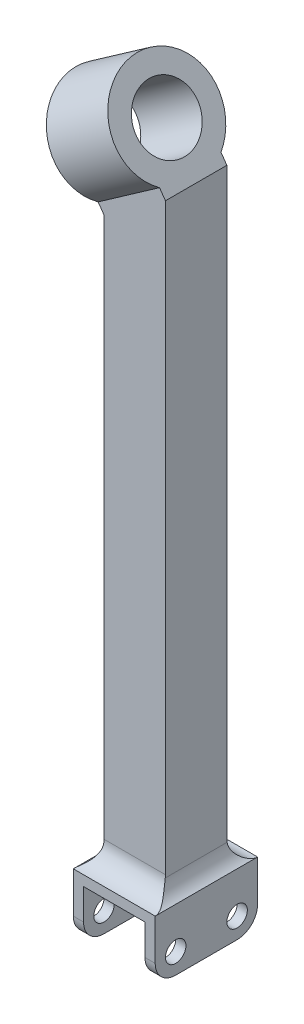
SolidWorks part; units mm, degrees
ref_plane "Front Plane" through (0, 0, 0) normal (0, 0, 1) x (1, 0, 0)
ref_plane "Top Plane" through (0, 0, 0) normal (0, 1, 0) x (1, 0, 0)
ref_plane "Right Plane" through (0, 0, 0) normal (1, 0, 0) x (0, 0, -1)
sketch "Sketch1" plane through (0, 0, 0) normal (0, 0, 1) x (1, 0, 0)
  line L0 (0, 0) -> (30, 0)
  line L1 (30, 0) -> (30, 300)
  line L2 (30, 300) -> (1.3212, 340.9576)
  line L3 (1.3212, 340.9576) -> (-28.6788, 319.9514)
  line L4 (30, 300) -> (0, 278.9938) construction
  line L5 (0, 0) -> (0, 278.9938)
  line L6 (0, 278.9938) -> (-28.6788, 319.9514)
  dimension "D1" = 30
  dimension "D2" = 300
  dimension "D3" = 215
  dimension "D4" = 50
  dimension "D5" = 55
extrude "Boss-Extrude1" add sketch "Sketch1" along normal blind 50
sketch "Sketch2" plane through (161.0842, 112.7924, 0) normal (0.8192, 0.5736, 0) x (0, 0, -1)
  line L1 (-50, 278.5383) -> (0, 278.5383)
  line L2 (-50, 278.5383) -> (-50, 228.5383)
  line L3 (-50, 228.5383) -> (0, 228.5383)
  line L4 (0, 278.5383) -> (0, 228.5383)
  circle A0 centre (-25, 253.5383) radius 25
  circle A1 centre (-25, 253.5383) radius 15
sketch "Sketch3" plane through (0, 0, 50) normal (0, 0, 1) x (1, 0, 0)
  line L0 (30, 300) -> (0, 278.9938)
  line L1 (-28.6788, 319.9514) -> (0, 278.9938) construction
  line L2 (0, 278.9938) -> (0, 5)
  line L3 (0, 278.9938) -> (0, 0) construction
  line L4 (0, 5) -> (30, 5)
  line L5 (30, 0) -> (30, 300) construction
  line L6 (30, 5) -> (30, 300)
  line L7 (0, 0) -> (30, 0) construction
  dimension "D1" = 5
extrude "Cut-Extrude4" cut sketch "Sketch3" against normal blind 10
sketch "Sketch4" plane through (0, 0, 0) normal (0, 0, -1) x (-1, 0, 0)
  line L0 (-30, 300) -> (0, 278.9938)
  line L1 (0, 278.9938) -> (0, 5)
  line L2 (0, 278.9938) -> (0, 0) construction
  line L3 (0, 5) -> (-30, 5)
  line L4 (-30, 0) -> (-30, 300) construction
  line L5 (-30, 5) -> (-30, 300)
  line L6 (0, 0) -> (-30, 0) construction
  dimension "D1" = 5
extrude "Cut-Extrude5" cut sketch "Sketch4" against normal blind 10
sketch "Sketch6" plane through (161.0842, 112.7924, 0) normal (0.8192, 0.5736, 0) x (0, 0, -1)
  circle A0 centre (-25, 253.5383) radius 15
extrude "Cut-Extrude6" cut sketch "Sketch6" against normal through all
sketch "Sketch7" plane through (161.0842, 112.7924, 0) normal (0.8192, 0.5736, 0) x (0, 0, -1)
  line L0 (-40, 228.5383) -> (-40, 233.5383)
  line L2 (-10, 233.5383) -> (-10, 228.5383)
  line L3 (-10, 228.5383) -> (0, 228.5383)
  line L4 (-50, 278.5383) -> (0, 278.5383)
  line L5 (-50, 278.5383) -> (-50, 228.5383)
  line L6 (-50, 228.5383) -> (-40, 228.5383)
  line L7 (0, 278.5383) -> (0, 228.5383)
  arc A0 (-10, 233.5383) -> (-40, 233.5383) centre (-25, 253.5383) ccw
  line M3 (0, 228.5383) -> (0, 278.5383)
  line M4 (0, 278.5383) -> (-50, 278.5383)
  line M5 (-50, 278.5383) -> (-50, 228.5383)
  line M6 (-50, 228.5383) -> (-40, 228.5383)
  line M8 (-10, 228.5383) -> (0, 228.5383)
extrude "Cut-Extrude7" cut sketch "Sketch7" against normal through all contours A0 L5 L0 M6 | A0 L4 M5 | A0 L7 M4 | A0 L2 M8 M3 region at (26.2852, 305.3052, 46.1697) region at (26.2852, 305.3052, 3.8303) region at (4.5241, 336.3833, 5.5842) region at (4.5241, 336.3833, 44.4158)
sketch "Sketch8" plane through (0, 0, 50) normal (0, 0, 1) x (1, 0, 0)
  line L0 (30, 0) -> (30, 5) construction
  line L1 (0, 5) -> (30, 5)
  line L2 (0, 5) -> (0, 0)
  line L3 (0, 0) -> (30, 0)
  line L4 (30, 5) -> (30, 0)
  line L5 (0, 0) -> (30, 0) construction
extrude "Cut-Extrude8" cut sketch "Sketch8" against normal through all
sketch "Sketch9" plane through (0, 5, 0) normal (0, -1, 0) x (1, 0, 0)
  line L0 (0, 25) -> (30, 25) construction
  line L1 (-5, 50) -> (35, 50)
  line L2 (-5, 50) -> (-5, 0)
  line L3 (-5, 0) -> (35, 0)
  line L4 (35, 50) -> (35, 0)
  line L5 (0, 40) -> (0, 10) construction
  line L6 (30, 50) -> (30, 0) construction
  line L7 (30, 25) -> (15, 25) construction
  line L8 (15, 25) -> (15, 41.9335) construction
  dimension "D1" = 40
  dimension "D2" = 50
  dimension "D3" = 25
  dimension "D4" = 20
extrude "Boss-Extrude2" add sketch "Sketch9" along normal blind 30
fillet "Fillet1" radius 10 6 edges at (15, -25, 0) (15, -25, 50) (15, 5, 40) (0, 5, 25) (30, 5, 25) (15, 5, 10)
sketch "Sketch10" plane through (0, 0, 0) normal (0, 0, -1) x (-1, 0, 0)
  line L0 (5, -25) -> (-35, -25) construction
  line L1 (-30, -25) -> (0, -25)
  line L2 (-30, -25) -> (-30, 0)
  line L3 (-30, 0) -> (0, 0)
  line L4 (0, -25) -> (0, 0)
  line L5 (-35, -15) -> (-35, 5) construction
  dimension "D1" = 5
  dimension "D2" = 25
  dimension "D3" = 30
extrude "Cut-Extrude9" cut sketch "Sketch10" against normal through all
sketch "Sketch11" plane through (-5, 0, 0) normal (-1, 0, 0) x (0, 0, 1)
  line L0 (25, -25) -> (25, -15) construction
  line L1 (40, -25) -> (10, -25) construction
  line L2 (25, -15) -> (10, -15) construction
  circle A0 centre (10, -15) radius 5
  circle A1 centre (40, -15) radius 5
  dimension "D1" = 10
extrude "Cut-Extrude10" cut sketch "Sketch11" against normal through all
